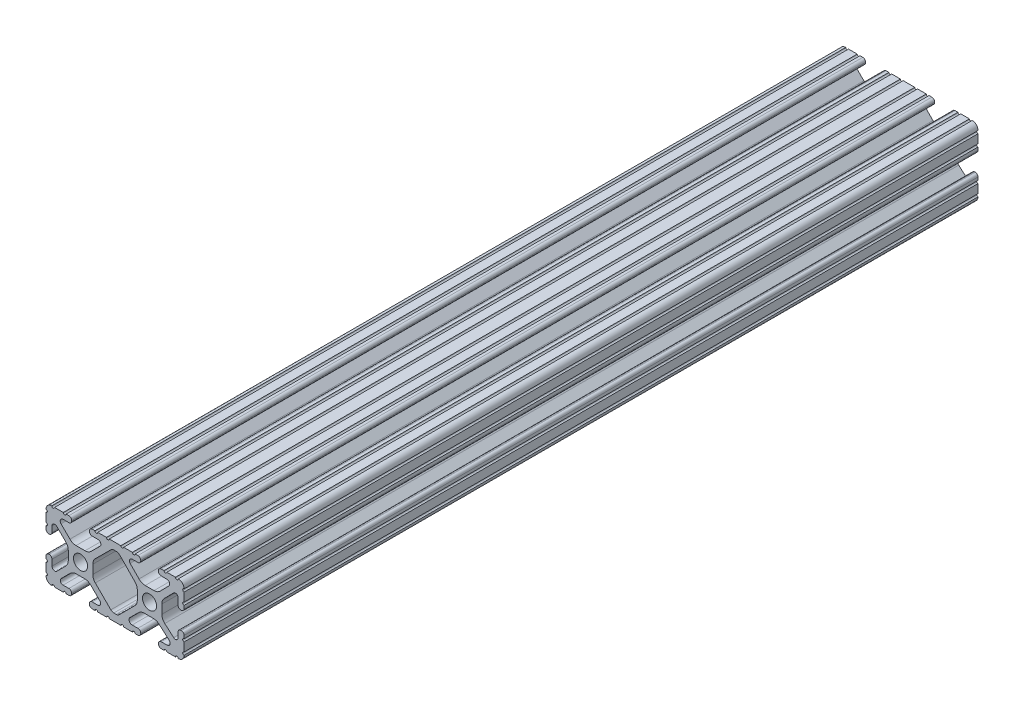
SolidWorks part; units mm, degrees
ref_plane "Front Plane" through (0, 0, 0) normal (0, 0, 1) x (1, 0, 0)
ref_plane "Top Plane" through (0, 0, 0) normal (0, 1, 0) x (1, 0, 0)
ref_plane "Right Plane" through (0, 0, 0) normal (1, 0, 0) x (0, 0, -1)
sketch "Sketch1" plane through (0, 0, 0) normal (0, 0, 1) x (1, 0, 0)
  line L0 (-7.2595, -3.8694) -> (-1.5457, -9.5728)
  line L1 (-8.1915, 1.6223) -> (-8.1915, -1.6223)
  line L2 (-1.504, 9.5765) -> (-7.252, 3.8768)
  line L3 (0.5515, 10.033) -> (-0.3952, 10.033)
  line L4 (7.2829, 3.8459) -> (1.6756, 9.5611)
  line L5 (8.1915, -1.6223) -> (8.1915, 1.6223)
  line L6 (1.5457, -9.5728) -> (7.2595, -3.8694)
  line L7 (-0.4332, -10.033) -> (0.4332, -10.033)
  line L8 (18.0171, 12.7) -> (16.9875, 12.7)
  line L9 (15.9385, 11.651) -> (15.9385, 11.5392)
  line L10 (16.9875, 10.4902) -> (19.1164, 10.4902)
  line L11 (19.8441, 8.7652) -> (16.619, 5.4551)
  line L12 (14.3449, 4.4958) -> (11.0833, 4.4958)
  line L13 (8.817, 5.4472) -> (5.5642, 8.7627)
  line L14 (6.2894, 10.4902) -> (8.4125, 10.4902)
  line L15 (9.4615, 11.5392) -> (9.4615, 11.651)
  line L16 (8.4125, 12.7) -> (7.3829, 12.7)
  line L17 (6.3669, 12.7) -> (3.1496, 12.7)
  line L18 (2.1336, 12.7) -> (-2.1336, 12.7)
  line L19 (-3.1496, 12.7) -> (-6.3669, 12.7)
  line L20 (-7.3829, 12.7) -> (-8.4125, 12.7)
  line L21 (-9.4615, 11.651) -> (-9.4615, 11.5392)
  line L22 (-8.4125, 10.4902) -> (-6.2836, 10.4902)
  line L23 (-5.5326, 8.6661) -> (-8.81, 5.4163)
  line L24 (-11.0455, 4.4958) -> (-14.3545, 4.4958)
  line L25 (-16.59, 5.4163) -> (-19.8674, 8.6661)
  line L26 (-19.1164, 10.4902) -> (-16.9875, 10.4902)
  line L27 (-15.9385, 11.5392) -> (-15.9385, 11.651)
  line L28 (-16.9875, 12.7) -> (-18.0171, 12.7)
  line L29 (-19.0331, 12.7) -> (-22.2504, 12.7)
  line L30 (-25.4, 9.5504) -> (-25.4, 6.3331)
  line L31 (-25.4, 5.3171) -> (-25.4, 4.2375)
  line L32 (-24.401, 3.2385) -> (-24.2392, 3.2385)
  line L33 (-23.1902, 4.2875) -> (-23.1902, 6.3347)
  line L34 (-21.434, 7.0665) -> (-18.148, 3.8082)
  line L35 (-17.2085, 1.5536) -> (-17.2085, -1.6952)
  line L36 (-18.1405, -3.9423) -> (-21.4316, -7.2274)
  line L37 (-23.1902, -6.498) -> (-23.1902, -4.2875)
  line L38 (-24.2392, -3.2385) -> (-24.351, -3.2385)
  line L39 (-25.4, -4.2875) -> (-25.4, -5.3171)
  line L40 (-25.4, -6.3331) -> (-25.4, -9.5504)
  line L41 (-22.2504, -12.7) -> (-19.0331, -12.7)
  line L42 (-18.0171, -12.7) -> (-16.9875, -12.7)
  line L43 (-15.9384, -11.651) -> (-15.9384, -11.5392)
  line L44 (-16.9875, -10.4902) -> (-19.1164, -10.4902)
  line L45 (-19.8341, -8.7551) -> (-16.4966, -5.4237)
  line L46 (-14.2536, -4.4958) -> (-11.1464, -4.4958)
  line L47 (-8.9034, -5.4237) -> (-5.5659, -8.7551)
  line L48 (-6.2836, -10.4902) -> (-8.4125, -10.4902)
  line L49 (-9.4616, -11.5392) -> (-9.4616, -11.651)
  line L50 (-8.4125, -12.7) -> (-7.3829, -12.7)
  line L51 (-6.3669, -12.7) -> (-3.1496, -12.7)
  line L52 (-2.1336, -12.7) -> (2.1336, -12.7)
  line L53 (3.1496, -12.7) -> (6.3669, -12.7)
  line L54 (7.3829, -12.7) -> (8.4125, -12.7)
  line L55 (9.4616, -11.651) -> (9.4616, -11.5392)
  line L56 (8.4125, -10.4902) -> (6.2894, -10.4902)
  line L57 (5.4807, -8.5353) -> (8.5979, -5.4237)
  line L58 (10.8409, -4.4958) -> (14.1026, -4.4958)
  line L59 (16.1879, -5.2766) -> (19.8682, -8.4822)
  line L60 (19.1164, -10.4902) -> (16.9875, -10.4902)
  line L61 (15.9384, -11.5392) -> (15.9384, -11.651)
  line L62 (16.9875, -12.7) -> (18.0171, -12.7)
  line L63 (19.0331, -12.7) -> (22.2504, -12.7)
  line L64 (25.4, -9.5504) -> (25.4, -6.3331)
  line L65 (25.4, -5.3171) -> (25.4, -4.2375)
  line L66 (24.401, -3.2385) -> (24.1892, -3.2385)
  line L67 (23.1902, -4.2375) -> (23.1902, -6.1559)
  line L68 (21.584, -6.8869) -> (18.2982, -4.025)
  line L69 (17.2085, -1.6308) -> (17.2085, 1.6308)
  line L70 (18.1094, 3.8465) -> (21.5263, 7.3534)
  line L71 (23.1902, 6.6769) -> (23.1902, 4.2375)
  line L72 (24.1892, 3.2385) -> (24.401, 3.2385)
  line L73 (25.4, 4.2375) -> (25.4, 5.3171)
  line L74 (25.4, 6.3332) -> (25.4, 9.5504)
  line L75 (22.2504, 12.7) -> (19.0331, 12.7)
  circle A0 centre (-12.7, 0) radius 2.6035
  circle A1 centre (12.7, 0) radius 2.6035
  arc A2 (-1.5457, -9.5728) -> (-0.4332, -10.033) centre (-0.4332, -8.4582) ccw
  arc A3 (-8.1915, -1.6223) -> (-7.2595, -3.8694) centre (-5.0165, -1.6223) ccw
  arc A4 (-7.252, 3.8768) -> (-8.1915, 1.6223) centre (-5.0165, 1.6223) ccw
  arc A5 (-0.3952, 10.033) -> (-1.504, 9.5765) centre (-0.3952, 8.4582) ccw
  arc A6 (1.6756, 9.5611) -> (0.5515, 10.033) centre (0.5515, 8.4582) ccw
  arc A7 (8.1915, 1.6223) -> (7.2829, 3.8459) centre (5.0165, 1.6223) ccw
  arc A8 (7.2595, -3.8694) -> (8.1915, -1.6223) centre (5.0165, -1.6223) ccw
  arc A9 (0.4332, -10.033) -> (1.5457, -9.5728) centre (0.4332, -8.4582) ccw
  arc A10 (18.0171, 12.7) -> (19.0331, 12.7) centre (18.5251, 12.7) ccw
  arc A11 (16.9875, 12.7) -> (15.9385, 11.651) centre (16.9875, 11.651) ccw
  arc A12 (15.9385, 11.5392) -> (16.9875, 10.4902) centre (16.9875, 11.5392) ccw
  arc A13 (19.8441, 8.7652) -> (19.1164, 10.4902) centre (19.1164, 9.4742) ccw
  arc A14 (14.3449, 4.4958) -> (16.619, 5.4551) centre (14.3449, 7.6708) ccw
  arc A15 (8.817, 5.4472) -> (11.0833, 4.4958) centre (11.0833, 7.6708) ccw
  arc A16 (6.2894, 10.4902) -> (5.5642, 8.7627) centre (6.2894, 9.4742) ccw
  arc A17 (8.4125, 10.4902) -> (9.4615, 11.5392) centre (8.4125, 11.5392) ccw
  arc A18 (9.4615, 11.651) -> (8.4125, 12.7) centre (8.4125, 11.651) ccw
  arc A19 (6.3669, 12.7) -> (7.3829, 12.7) centre (6.8749, 12.7) ccw
  arc A20 (2.1336, 12.7) -> (3.1496, 12.7) centre (2.6416, 12.7) ccw
  arc A21 (-3.1496, 12.7) -> (-2.1336, 12.7) centre (-2.6416, 12.7) ccw
  arc A22 (-7.3829, 12.7) -> (-6.3669, 12.7) centre (-6.8749, 12.7) ccw
  arc A23 (-8.4125, 12.7) -> (-9.4615, 11.651) centre (-8.4125, 11.651) ccw
  arc A24 (-9.4615, 11.5392) -> (-8.4125, 10.4902) centre (-8.4125, 11.5392) ccw
  arc A25 (-5.5326, 8.6661) -> (-6.2836, 10.4902) centre (-6.2836, 9.4235) ccw
  arc A26 (-11.0455, 4.4958) -> (-8.81, 5.4163) centre (-11.0455, 7.6708) ccw
  arc A27 (-16.59, 5.4163) -> (-14.3545, 4.4958) centre (-14.3545, 7.6708) ccw
  arc A28 (-19.1164, 10.4902) -> (-19.8674, 8.6661) centre (-19.1164, 9.4235) ccw
  arc A29 (-16.9875, 10.4902) -> (-15.9385, 11.5392) centre (-16.9875, 11.5392) ccw
  arc A30 (-15.9385, 11.651) -> (-16.9875, 12.7) centre (-16.9875, 11.651) ccw
  arc A31 (-19.0331, 12.7) -> (-18.0171, 12.7) centre (-18.5251, 12.7) ccw
  arc A32 (-23.2664, 12.6998) -> (-22.2504, 12.7) centre (-22.7584, 12.7) ccw
  arc A33 (-23.2664, 12.6998) -> (-25.3998, 10.5664) centre (-23.2918, 10.5918) ccw
  arc A34 (-25.4, 9.5504) -> (-25.3998, 10.5664) centre (-25.4, 10.0584) ccw
  arc A35 (-25.4, 5.3171) -> (-25.4, 6.3331) centre (-25.4, 5.8251) ccw
  arc A36 (-25.4, 4.2375) -> (-24.401, 3.2385) centre (-24.401, 4.2375) ccw
  arc A37 (-24.2392, 3.2385) -> (-23.1902, 4.2875) centre (-24.2392, 4.2875) ccw
  arc A38 (-21.434, 7.0665) -> (-23.1902, 6.3347) centre (-22.1596, 6.3347) ccw
  arc A39 (-17.2085, 1.5536) -> (-18.148, 3.8082) centre (-20.3835, 1.5536) ccw
  arc A40 (-18.1405, -3.9423) -> (-17.2085, -1.6952) centre (-20.3835, -1.6952) ccw
  arc A41 (-23.1902, -6.498) -> (-21.4316, -7.2274) centre (-22.1596, -6.498) ccw
  arc A42 (-23.1902, -4.2875) -> (-24.2392, -3.2385) centre (-24.2392, -4.2875) ccw
  arc A43 (-24.351, -3.2385) -> (-25.4, -4.2875) centre (-24.351, -4.2875) ccw
  arc A44 (-25.4, -6.3331) -> (-25.4, -5.3171) centre (-25.4, -5.8251) ccw
  arc A45 (-25.3998, -10.5664) -> (-25.4, -9.5504) centre (-25.4, -10.0584) ccw
  arc A46 (-25.3998, -10.5664) -> (-23.2664, -12.6998) centre (-23.2918, -10.5918) ccw
  arc A47 (-22.2504, -12.7) -> (-23.2664, -12.6998) centre (-22.7584, -12.7) ccw
  arc A48 (-18.0171, -12.7) -> (-19.0331, -12.7) centre (-18.5251, -12.7) ccw
  arc A49 (-16.9875, -12.7) -> (-15.9384, -11.651) centre (-16.9875, -11.651) ccw
  arc A50 (-15.9384, -11.5392) -> (-16.9875, -10.4902) centre (-16.9875, -11.5392) ccw
  arc A51 (-19.8341, -8.7551) -> (-19.1164, -10.4902) centre (-19.1164, -9.4742) ccw
  arc A52 (-14.2536, -4.4958) -> (-16.4966, -5.4237) centre (-14.2536, -7.6708) ccw
  arc A53 (-8.9034, -5.4237) -> (-11.1464, -4.4958) centre (-11.1464, -7.6708) ccw
  arc A54 (-6.2836, -10.4902) -> (-5.5659, -8.7551) centre (-6.2836, -9.4742) ccw
  arc A55 (-8.4125, -10.4902) -> (-9.4616, -11.5392) centre (-8.4125, -11.5392) ccw
  arc A56 (-9.4616, -11.651) -> (-8.4125, -12.7) centre (-8.4125, -11.651) ccw
  arc A57 (-6.3669, -12.7) -> (-7.3829, -12.7) centre (-6.8749, -12.7) ccw
  arc A58 (-2.1336, -12.7) -> (-3.1496, -12.7) centre (-2.6416, -12.7) ccw
  arc A59 (3.1496, -12.7) -> (2.1336, -12.7) centre (2.6416, -12.7) ccw
  arc A60 (7.3829, -12.7) -> (6.3669, -12.7) centre (6.8749, -12.7) ccw
  arc A61 (8.4125, -12.7) -> (9.4616, -11.651) centre (8.4125, -11.651) ccw
  arc A62 (9.4616, -11.5392) -> (8.4125, -10.4902) centre (8.4125, -11.5392) ccw
  arc A63 (5.4807, -8.5353) -> (6.2894, -10.4902) centre (6.2894, -9.3455) ccw
  arc A64 (10.8409, -4.4958) -> (8.5979, -5.4237) centre (10.8409, -7.6708) ccw
  arc A65 (16.1879, -5.2766) -> (14.1026, -4.4958) centre (14.1026, -7.6708) ccw
  arc A66 (19.1164, -10.4902) -> (19.8682, -8.4822) centre (19.1164, -9.3455) ccw
  arc A67 (16.9875, -10.4902) -> (15.9384, -11.5392) centre (16.9875, -11.5392) ccw
  arc A68 (15.9384, -11.651) -> (16.9875, -12.7) centre (16.9875, -11.651) ccw
  arc A69 (19.0331, -12.7) -> (18.0171, -12.7) centre (18.5251, -12.7) ccw
  arc A70 (23.2664, -12.6998) -> (22.2504, -12.7) centre (22.7584, -12.7) ccw
  arc A71 (23.2664, -12.6998) -> (25.3998, -10.5664) centre (23.2918, -10.5918) ccw
  arc A72 (25.4, -9.5504) -> (25.3998, -10.5664) centre (25.4, -10.0584) ccw
  arc A73 (25.4, -5.3171) -> (25.4, -6.3331) centre (25.4, -5.8251) ccw
  arc A74 (25.4, -4.2375) -> (24.401, -3.2385) centre (24.401, -4.2375) ccw
  arc A75 (24.1892, -3.2385) -> (23.1902, -4.2375) centre (24.1892, -4.2375) ccw
  arc A76 (21.584, -6.8869) -> (23.1902, -6.1559) centre (22.2207, -6.1559) ccw
  arc A77 (17.2085, -1.6308) -> (18.2982, -4.025) centre (20.3835, -1.6308) ccw
  arc A78 (18.1094, 3.8465) -> (17.2085, 1.6308) centre (20.3835, 1.6308) ccw
  arc A79 (23.1902, 6.6769) -> (21.5263, 7.3534) centre (22.2207, 6.6769) ccw
  arc A80 (23.1902, 4.2375) -> (24.1892, 3.2385) centre (24.1892, 4.2375) ccw
  arc A81 (24.401, 3.2385) -> (25.4, 4.2375) centre (24.401, 4.2375) ccw
  arc A82 (25.4, 6.3332) -> (25.4, 5.3171) centre (25.4, 5.8251) ccw
  arc A83 (25.3998, 10.5664) -> (25.4, 9.5504) centre (25.4, 10.0584) ccw
  arc A84 (25.3998, 10.5664) -> (23.2664, 12.6998) centre (23.2918, 10.5918) ccw
  arc A85 (22.2504, 12.7) -> (23.2664, 12.6998) centre (22.7584, 12.7) ccw
  point P248 (0, 10.033)
extrude "Boss-Extrude1" add sketch "Sketch1" along normal mid plane 292.1
ref_plane "Plane1" through (0, 0, 0) normal (0, -1, 0) x (-1, 0, 0)
ref_axis "Axis1" through (12.7, 0, 146.05) along (0, 0, -1)
ref_plane "Plane2" through (12.7, 0, 0) normal (-1, 0, 0) x (0, 0, -1)
